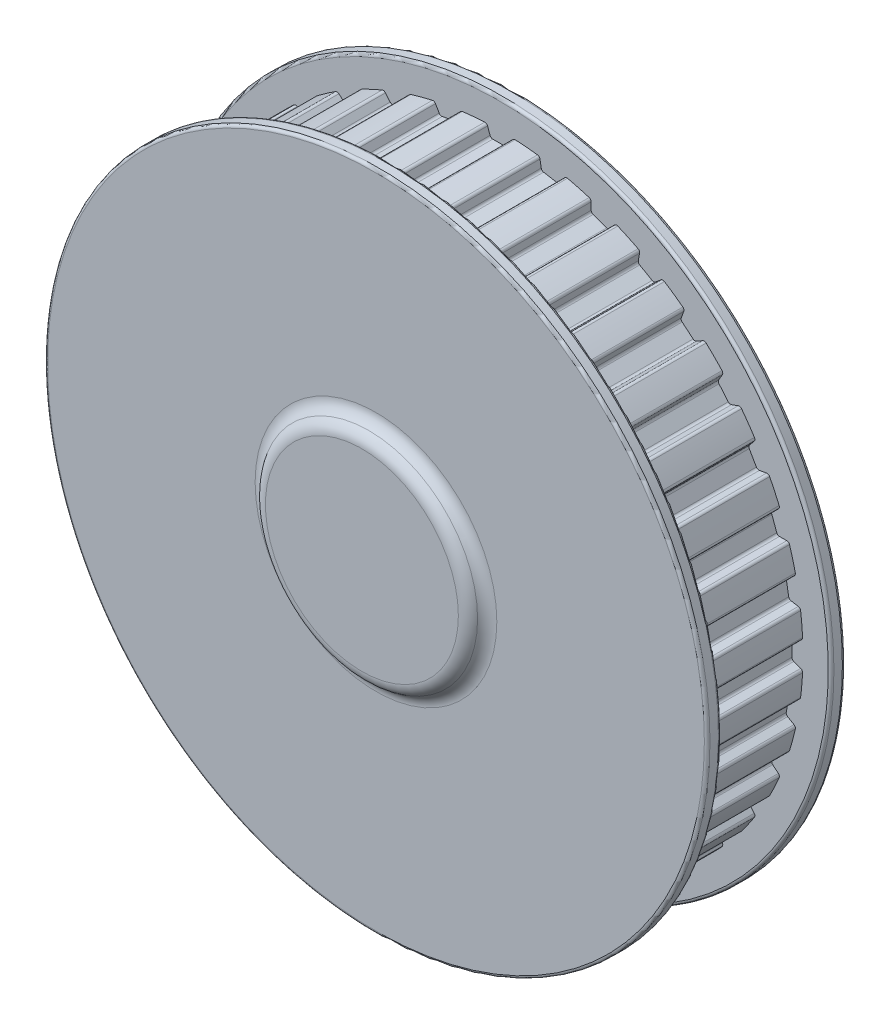
SolidWorks part; units mm, degrees
ref_plane "Front Plane" through (0, 0, 0) normal (0, 0, 1) x (1, 0, 0)
ref_plane "Top Plane" through (0, 0, 0) normal (0, 1, 0) x (1, 0, 0)
ref_plane "Right Plane" through (0, 0, 0) normal (1, 0, 0) x (0, 0, -1)
sketch "Sketch1" plane through (0, 0, 0) normal (0, 1, 0) x (1, 0, 0)
  line L0 (0, 36.1296) -> (0, -19.4741) construction
sketch "Sketch7" plane through (0, 0, 0) normal (0, 0, 1) x (1, 0, 0)
  line L0 (0, 0) -> (0, 52.7795) construction
  line L1 (-2.325, 53.7345) -> (-2.9401, 55.4245) construction
  line L2 (-2.325, 53.7345) -> (-1.6298, 51.8245) construction
  line L3 (-1.6298, 51.8245) -> (1.6298, 51.8245) construction
  line L4 (1.6298, 51.8245) -> (2.325, 53.7345) construction
  line L5 (2.325, 53.7345) -> (-2.325, 53.7345) construction
  line L6 (0, 51.8245) -> (0, 53.7345) construction
  line L7 (2.325, 53.7345) -> (2.9401, 55.4245) construction
  line L8 (-2.9401, 55.4245) -> (2.9401, 55.4245) construction
  line L9 (0, 0) -> (9.1651, 51.9776) construction
  line L10 (9.1651, 51.9776) -> (9.3396, 52.9676) construction
  line L11 (0, 53.7345) -> (0, 53.7847) construction
  line L12 (0, 53.7847) -> (0, 55.5024) construction
  line L13 (0, 54.6436) -> (9.4888, 53.8134) construction
  line L14 (9.3396, 52.9676) -> (9.6379, 54.6592) construction
  circle A1 centre (0, 0) radius 52.7795 construction
  circle A2 centre (-1.2727, 52.3345) radius 0.51 construction
  circle A3 centre (1.2727, 52.3345) radius 0.51 construction
  circle A4 centre (0, 0) radius 53.7847
  circle A5 centre (0, 0) radius 55.5024 construction
  dimension "D3" = 40
  dimension "D6" = 1.02
  dimension "D1" = 3.6
  dimension "D2" = 10
  dimension "D7" = 9.525
  dimension "D4" = 1.91
  dimension "D5" = 4.65
extrude "Boss-Extrude1" add sketch "Sketch7" along normal blind 7.25 and the other way blind 7.25 contours A4 region at (0, 0, 0)
sketch "Sketch14" plane through (0, 0, 0) normal (1, 0, 0) x (0, 0, -1)
  line L0 (-18, 0) -> (-18, 10)
  line L1 (-18, 0) -> (0, 0)
  line L2 (0, 0) -> (0, 19)
  line L3 (0, 19) -> (-7.25, 19)
  line L4 (-7.25, 19) -> (-18, 10)
  line L5 (-7.25, 53.7847) -> (-7.25, -53.7847) construction
  line L6 (-18, 6.7395) -> (-3.3555, 19) construction
  arc A0 (-7.25, 19) -> (-18, 10) centre (-18.1316, 21.0773) cw
  dimension "D1" = 10
  dimension "D2" = 19
  dimension "D3" = 18
  dimension "D4" = 2.5
revolve "Revolve1" add sketch "Sketch14" angle 360 about L0 region at (0, 7.5733, 7.5341) region at (0, 9.2725, 16.1663) region at (0, 17.2765, 6.6188)
sketch "Sketch9" plane through (0, 0, 0) normal (0, 0, 1) x (1, 0, 0)
  line L0 (2, 0) -> (-2, 0) construction
  line L1 (-2, 0) -> (-2, 7.5) construction
  line L2 (-2, 7.5) -> (2, 7.5) construction
  line L3 (2, 7.5) -> (2, 0) construction
  circle A0 centre (0, 0) radius 6 construction
  dimension "D1" = 12
  dimension "D2" = 4
  dimension "D3" = 7.5
sketch "Sketch10" plane through (0, 0, 0) normal (0, 0, 1) x (1, 0, 0)
  line L0 (2, 0) -> (-2, 0) construction
  line L1 (-2.2, 7.7) -> (2.2, 7.7)
  line L2 (-2.2, 7.7) -> (-2.2, 0)
  line L3 (-2.2, 0) -> (2.2, 0)
  line L4 (2.2, 7.7) -> (2.2, 0)
  line L5 (-2, 7.5) -> (2, 7.5) construction
  line L6 (2, 7.5) -> (2, 0) construction
  circle A0 centre (0, 0) radius 6.2
  circle A1 centre (0, 0) radius 6 construction
  dimension "D1" = 0.2
  dimension "D2" = 0.2
  dimension "D3" = 0.2
extrude "Cut-Extrude3" cut sketch "Sketch10" against normal through all both and the other way through all contours A0 L4 L1 L2 | L2 A0 L4 L3 | L4 A0 L2 L3 region at (0, 6.8793, 0) region at (0, 3.0348, 0) region at (0, -0.8613, 0)
sketch "Sketch11" plane through (0, 0, 0) normal (0, 1, 0) x (1, 0, 0)
  line L0 (53.7847, 7.25) -> (-53.7847, 7.25) construction
  line L1 (11, 7.25) -> (17.5, 7.25)
  line L2 (11, 7.25) -> (11, 4.75)
  line L3 (11, 4.75) -> (17.5, 4.75)
  line L4 (17.5, 7.25) -> (17.5, 4.75)
  line L5 (-53.7847, -7.25) -> (53.7847, -7.25) construction
  line L6 (11, -7.25) -> (17.5, -7.25)
  line L7 (11, -7.25) -> (11, -4.75)
  line L8 (11, -4.75) -> (17.5, -4.75)
  line L9 (17.5, -7.25) -> (17.5, -4.75)
  line L11 (11, 4.75) -> (11, -4.75) construction
  line L12 (17.5, -4.75) -> (17.5, 4.75) construction
  line L13 (6.2, 7.25) -> (-6.2, 7.25) construction
  line L14 (0, 7.25) -> (22.5, 7.25)
  line L15 (0, 7.25) -> (0, -7.25)
  line L16 (0, -7.25) -> (22.5, -7.25)
  line L17 (22.5, 7.25) -> (22.5, -7.25)
  line L18 (-6.2, -7.25) -> (6.2, -7.25) construction
  line L19 (6, 7.25) -> (6, -7.25) construction
  dimension "D1" = 22.5
  dimension "D2" = 6
  dimension "D3" = 5
  dimension "D4" = 5
  dimension "D5" = 2.5
sketch "Sketch15" plane through (0, 0, -7.25) normal (0, 0, -1) x (-1, 0, 0)
  circle A0 centre (0, 0) radius 8.0081
  circle A1 centre (0, 0) radius 2.25
  dimension "D1" = 4.5
extrude "Boss-Extrude2" add sketch "Sketch15" against normal blind 5.5
sketch "Sketch16" plane through (0, 0, -7.25) normal (0, 0, -1) x (-1, 0, 0)
  circle A0 centre (0, 0) radius 5
  dimension "D1" = 10
extrude "Cut-Extrude4" cut sketch "Sketch16" against normal blind 3
sketch "Sketch17" plane through (0, 0, -7.25) normal (0, 0, -1) x (-1, 0, 0)
  circle A0 centre (0, 0) radius 53.7847
  circle A1 centre (0, 0) radius 53.7847 construction
  circle A2 centre (0, 0) radius 5
  circle A3 centre (0, 0) radius 5 construction
extrude "Boss-Extrude3" add sketch "Sketch17" along normal blind 7.5
sketch "Sketch8" plane through (0, 0, 0) normal (0, 0, 1) x (1, 0, 0)
  line L6 (-1.6298, 51.8245) -> (-2.3433, 53.7847)
  line L7 (-2.3433, 53.7847) -> (2.3433, 53.7847)
  line L8 (2.3433, 53.7847) -> (1.6298, 51.8245)
  line L9 (1.6298, 51.8245) -> (-1.6298, 51.8245)
  line L10 (-2.325, 53.7345) -> (-1.6298, 51.8245) construction
  line L11 (1.6298, 51.8245) -> (2.325, 53.7345) construction
  line L12 (7.3942, 51.3201) -> (7.0319, 53.3745)
  line L13 (7.0319, 53.3745) -> (11.6473, 52.5607)
  line L14 (11.6473, 52.5607) -> (10.6043, 50.7541)
  line L15 (10.6043, 50.7541) -> (7.3942, 51.3201)
  line L16 (16.1935, 49.2565) -> (16.1935, 51.3426)
  line L17 (16.1935, 51.3426) -> (20.5974, 49.7397)
  line L18 (20.5974, 49.7397) -> (19.2565, 48.1416)
  line L19 (19.2565, 48.1416) -> (16.1935, 49.2565)
  line L20 (24.5008, 45.6962) -> (24.863, 47.7506)
  line L21 (24.863, 47.7506) -> (28.9217, 45.4073)
  line L22 (28.9217, 45.4073) -> (27.3237, 44.0664)
  line L23 (27.3237, 44.0664) -> (24.5008, 45.6962)
  line L24 (32.0636, 40.7475) -> (32.7771, 42.7077)
  line L25 (32.7771, 42.7077) -> (36.3672, 39.6953)
  line L26 (36.3672, 39.6953) -> (34.5606, 38.6522)
  line L27 (34.5606, 38.6522) -> (32.0636, 40.7475)
  line L28 (38.6522, 34.5606) -> (39.6953, 36.3672)
  line L29 (39.6953, 36.3672) -> (42.7077, 32.7771)
  line L30 (42.7077, 32.7771) -> (40.7475, 32.0636)
  line L31 (40.7475, 32.0636) -> (38.6522, 34.5606)
  line L32 (44.0664, 27.3237) -> (45.4073, 28.9217)
  line L33 (45.4073, 28.9217) -> (47.7506, 24.863)
  line L34 (47.7506, 24.863) -> (45.6962, 24.5008)
  line L35 (45.6962, 24.5008) -> (44.0664, 27.3237)
  line L36 (48.1416, 19.2565) -> (49.7397, 20.5974)
  line L37 (49.7397, 20.5974) -> (51.3426, 16.1935)
  line L38 (51.3426, 16.1935) -> (49.2565, 16.1935)
  line L39 (49.2565, 16.1935) -> (48.1416, 19.2565)
  line L40 (50.7541, 10.6043) -> (52.5607, 11.6473)
  line L41 (52.5607, 11.6473) -> (53.3745, 7.0319)
  line L42 (53.3745, 7.0319) -> (51.3201, 7.3942)
  line L43 (51.3201, 7.3942) -> (50.7541, 10.6043)
  line L44 (51.8245, 1.6298) -> (53.7847, 2.3433)
  line L45 (53.7847, 2.3433) -> (53.7847, -2.3433)
  line L46 (53.7847, -2.3433) -> (51.8245, -1.6298)
  line L47 (51.8245, -1.6298) -> (51.8245, 1.6298)
  line L48 (51.3201, -7.3942) -> (53.3745, -7.0319)
  line L49 (53.3745, -7.0319) -> (52.5607, -11.6473)
  line L50 (52.5607, -11.6473) -> (50.7541, -10.6043)
  line L51 (50.7541, -10.6043) -> (51.3201, -7.3942)
  line L52 (49.2565, -16.1935) -> (51.3426, -16.1935)
  line L53 (51.3426, -16.1935) -> (49.7397, -20.5974)
  line L54 (49.7397, -20.5974) -> (48.1416, -19.2565)
  line L55 (48.1416, -19.2565) -> (49.2565, -16.1935)
  line L56 (45.6962, -24.5008) -> (47.7506, -24.863)
  line L57 (47.7506, -24.863) -> (45.4073, -28.9217)
  line L58 (45.4073, -28.9217) -> (44.0664, -27.3237)
  line L59 (44.0664, -27.3237) -> (45.6962, -24.5008)
  line L60 (40.7475, -32.0636) -> (42.7077, -32.7771)
  line L61 (42.7077, -32.7771) -> (39.6953, -36.3672)
  line L62 (39.6953, -36.3672) -> (38.6522, -34.5606)
  line L63 (38.6522, -34.5606) -> (40.7475, -32.0636)
  line L64 (34.5606, -38.6522) -> (36.3672, -39.6953)
  line L65 (36.3672, -39.6953) -> (32.7771, -42.7077)
  line L66 (32.7771, -42.7077) -> (32.0636, -40.7475)
  line L67 (32.0636, -40.7475) -> (34.5606, -38.6522)
  line L68 (27.3237, -44.0664) -> (28.9217, -45.4073)
  line L69 (28.9217, -45.4073) -> (24.863, -47.7506)
  line L70 (24.863, -47.7506) -> (24.5008, -45.6962)
  line L71 (24.5008, -45.6962) -> (27.3237, -44.0664)
  line L72 (19.2565, -48.1416) -> (20.5974, -49.7397)
  line L73 (20.5974, -49.7397) -> (16.1935, -51.3426)
  line L74 (16.1935, -51.3426) -> (16.1935, -49.2565)
  line L75 (16.1935, -49.2565) -> (19.2565, -48.1416)
  line L76 (10.6043, -50.7541) -> (11.6473, -52.5607)
  line L77 (11.6473, -52.5607) -> (7.0319, -53.3745)
  line L78 (7.0319, -53.3745) -> (7.3942, -51.3201)
  line L79 (7.3942, -51.3201) -> (10.6043, -50.7541)
  line L80 (1.6298, -51.8245) -> (2.3433, -53.7847)
  line L81 (2.3433, -53.7847) -> (-2.3433, -53.7847)
  line L82 (-2.3433, -53.7847) -> (-1.6298, -51.8245)
  line L83 (-1.6298, -51.8245) -> (1.6298, -51.8245)
  line L84 (-7.3942, -51.3201) -> (-7.0319, -53.3745)
  line L85 (-7.0319, -53.3745) -> (-11.6473, -52.5607)
  line L86 (-11.6473, -52.5607) -> (-10.6043, -50.7541)
  line L87 (-10.6043, -50.7541) -> (-7.3942, -51.3201)
  line L88 (-16.1935, -49.2565) -> (-16.1935, -51.3426)
  line L89 (-16.1935, -51.3426) -> (-20.5974, -49.7397)
  line L90 (-20.5974, -49.7397) -> (-19.2565, -48.1416)
  line L91 (-19.2565, -48.1416) -> (-16.1935, -49.2565)
  line L92 (-24.5008, -45.6962) -> (-24.863, -47.7506)
  line L93 (-24.863, -47.7506) -> (-28.9217, -45.4073)
  line L94 (-28.9217, -45.4073) -> (-27.3237, -44.0664)
  line L95 (-27.3237, -44.0664) -> (-24.5008, -45.6962)
  line L96 (-32.0636, -40.7475) -> (-32.7771, -42.7077)
  line L97 (-32.7771, -42.7077) -> (-36.3672, -39.6953)
  line L98 (-36.3672, -39.6953) -> (-34.5606, -38.6522)
  line L99 (-34.5606, -38.6522) -> (-32.0636, -40.7475)
  line L100 (-38.6522, -34.5606) -> (-39.6953, -36.3672)
  line L101 (-39.6953, -36.3672) -> (-42.7077, -32.7771)
  line L102 (-42.7077, -32.7771) -> (-40.7475, -32.0636)
  line L103 (-40.7475, -32.0636) -> (-38.6522, -34.5606)
  line L104 (-44.0664, -27.3237) -> (-45.4073, -28.9217)
  line L105 (-45.4073, -28.9217) -> (-47.7506, -24.863)
  line L106 (-47.7506, -24.863) -> (-45.6962, -24.5008)
  line L107 (-45.6962, -24.5008) -> (-44.0664, -27.3237)
  line L108 (-48.1416, -19.2565) -> (-49.7397, -20.5974)
  line L109 (-49.7397, -20.5974) -> (-51.3426, -16.1935)
  line L110 (-51.3426, -16.1935) -> (-49.2565, -16.1935)
  line L111 (-49.2565, -16.1935) -> (-48.1416, -19.2565)
  line L112 (-50.7541, -10.6043) -> (-52.5607, -11.6473)
  line L113 (-52.5607, -11.6473) -> (-53.3745, -7.0319)
  line L114 (-53.3745, -7.0319) -> (-51.3201, -7.3942)
  line L115 (-51.3201, -7.3942) -> (-50.7541, -10.6043)
  line L116 (-51.8245, -1.6298) -> (-53.7847, -2.3433)
  line L117 (-53.7847, -2.3433) -> (-53.7847, 2.3433)
  line L118 (-53.7847, 2.3433) -> (-51.8245, 1.6298)
  line L119 (-51.8245, 1.6298) -> (-51.8245, -1.6298)
  line L120 (-51.3201, 7.3942) -> (-53.3745, 7.0319)
  line L121 (-53.3745, 7.0319) -> (-52.5607, 11.6473)
  line L122 (-52.5607, 11.6473) -> (-50.7541, 10.6043)
  line L123 (-50.7541, 10.6043) -> (-51.3201, 7.3942)
  line L124 (-49.2565, 16.1935) -> (-51.3426, 16.1935)
  line L125 (-51.3426, 16.1935) -> (-49.7397, 20.5974)
  line L126 (-49.7397, 20.5974) -> (-48.1416, 19.2565)
  line L127 (-48.1416, 19.2565) -> (-49.2565, 16.1935)
  line L128 (-45.6962, 24.5008) -> (-47.7506, 24.863)
  line L129 (-47.7506, 24.863) -> (-45.4073, 28.9217)
  line L130 (-45.4073, 28.9217) -> (-44.0664, 27.3237)
  line L131 (-44.0664, 27.3237) -> (-45.6962, 24.5008)
  line L132 (-40.7475, 32.0636) -> (-42.7077, 32.7771)
  line L133 (-42.7077, 32.7771) -> (-39.6953, 36.3672)
  line L134 (-39.6953, 36.3672) -> (-38.6522, 34.5606)
  line L135 (-38.6522, 34.5606) -> (-40.7475, 32.0636)
  line L136 (-34.5606, 38.6522) -> (-36.3672, 39.6953)
  line L137 (-36.3672, 39.6953) -> (-32.7771, 42.7077)
  line L138 (-32.7771, 42.7077) -> (-32.0636, 40.7475)
  line L139 (-32.0636, 40.7475) -> (-34.5606, 38.6522)
  line L140 (-27.3237, 44.0664) -> (-28.9217, 45.4073)
  line L141 (-28.9217, 45.4073) -> (-24.863, 47.7506)
  line L142 (-24.863, 47.7506) -> (-24.5008, 45.6962)
  line L143 (-24.5008, 45.6962) -> (-27.3237, 44.0664)
  line L144 (-19.2565, 48.1416) -> (-20.5974, 49.7397)
  line L145 (-20.5974, 49.7397) -> (-16.1935, 51.3426)
  line L146 (-16.1935, 51.3426) -> (-16.1935, 49.2565)
  line L147 (-16.1935, 49.2565) -> (-19.2565, 48.1416)
  line L148 (-10.6043, 50.7541) -> (-11.6473, 52.5607)
  line L149 (-11.6473, 52.5607) -> (-7.0319, 53.3745)
  line L150 (-7.0319, 53.3745) -> (-7.3942, 51.3201)
  line L151 (-7.3942, 51.3201) -> (-10.6043, 50.7541)
  circle A0 centre (0, 0) radius 53.7847 construction
  point P119 (0, 0)
  dimension "D1" = 36
extrude "Cut-Extrude2" cut sketch "Sketch8" against normal through all both and the other way through all
fillet "Fillet2" radius 0.51 144 edges at (32.7588, -42.6575, -3.75) (36.3209, -39.6685, -3.75) (39.6685, -36.3209, -3.75) (42.6575, -32.7588, -3.75) (45.3729, -28.8807, -3.75) (47.6979, -24.8537, -3.75) (49.6987, -20.5631, -3.75) (51.2891, -16.1935, -3.75) (52.5144, -11.6206, -3.75) (53.3218, -7.0412, -3.75) (53.7345, -2.325, -3.75) (53.7345, 2.325, -3.75) (53.3218, 7.0412, -3.75) (52.5144, 11.6206, -3.75) (51.2891, 16.1935, -3.75) (49.6987, 20.5631, -3.75) (47.6979, 24.8537, -3.75) (45.3729, 28.8807, -3.75) (42.6575, 32.7588, -3.75) (39.6685, 36.3209, -3.75) (36.3209, 39.6685, -3.75) (32.7588, 42.6575, -3.75) (28.8807, 45.3729, -3.75) (24.8537, 47.6979, -3.75) (20.5631, 49.6987, -3.75) (16.1935, 51.2891, -3.75) (11.6206, 52.5144, -3.75) (7.0412, 53.3218, -3.75) (2.325, 53.7345, -3.75) (32.0636, -40.7475, -3.75) (34.5606, -38.6522, -3.75) (38.6522, -34.5606, -3.75) (40.7475, -32.0636, -3.75) (44.0664, -27.3237, -3.75) (45.6962, -24.5008, -3.75) (48.1416, -19.2565, -3.75) (49.2565, -16.1935, -3.75) (50.7541, -10.6043, -3.75) (51.3201, -7.3942, -3.75) (51.8245, -1.6298, -3.75) (51.8245, 1.6298, -3.75) (51.3201, 7.3942, -3.75) (50.7541, 10.6043, -3.75) (49.2565, 16.1935, -3.75) (48.1416, 19.2565, -3.75) (45.6962, 24.5008, -3.75) (44.0664, 27.3237, -3.75) (40.7475, 32.0636, -3.75) (38.6522, 34.5606, -3.75) (34.5606, 38.6522, -3.75) (32.0636, 40.7475, -3.75) (27.3237, 44.0664, -3.75) (24.5008, 45.6962, -3.75) (19.2565, 48.1416, -3.75) (16.1935, 49.2565, -3.75) (10.6043, 50.7541, -3.75) (7.3942, 51.3201, -3.75) (1.6298, 51.8245, -3.75) (-1.6298, 51.8245, -3.75) (-2.325, 53.7345, -3.75) (-11.6206, -52.5144, -3.75) (-10.6043, -50.7541, -3.75) (-7.3942, -51.3201, -3.75) (-7.0412, -53.3218, -3.75) (-2.325, -53.7345, -3.75) (-1.6298, -51.8245, -3.75) (1.6298, -51.8245, -3.75) (2.325, -53.7345, -3.75) (7.0412, -53.3218, -3.75) (7.3942, -51.3201, -3.75) (10.6043, -50.7541, -3.75) (11.6206, -52.5144, -3.75) (16.1935, -51.2891, -3.75) (16.1935, -49.2565, -3.75) (19.2565, -48.1416, -3.75) (20.5631, -49.6987, -3.75) (24.8537, -47.6979, -3.75) (24.5008, -45.6962, -3.75) (27.3237, -44.0664, -3.75) (28.8807, -45.3729, -3.75) (-16.1935, -51.2891, -3.75) (-16.1935, -49.2565, -3.75) (-19.2565, -48.1416, -3.75) (-20.5631, -49.6987, -3.75) (-24.8537, -47.6979, -3.75) (-24.5008, -45.6962, -3.75) (-27.3237, -44.0664, -3.75) (-28.8807, -45.3729, -3.75) (-32.7588, -42.6575, -3.75) (-32.0636, -40.7475, -3.75) (-34.5606, -38.6522, -3.75) (-36.3209, -39.6685, -3.75) (-39.6685, -36.3209, -3.75) (-38.6522, -34.5606, -3.75) (-40.7475, -32.0636, -3.75) (-42.6575, -32.7588, -3.75) (-34.5606, 38.6522, -3.75) (-32.0636, 40.7475, -3.75) (-32.7588, 42.6575, -3.75) (-28.8807, 45.3729, -3.75) (-27.3237, 44.0664, -3.75) (-24.5008, 45.6962, -3.75) (-24.8537, 47.6979, -3.75) (-20.5631, 49.6987, -3.75) (-19.2565, 48.1416, -3.75) (-16.1935, 49.2565, -3.75) (-16.1935, 51.2891, -3.75) (-11.6206, 52.5144, -3.75) (-10.6043, 50.7541, -3.75) (-7.3942, 51.3201, -3.75) (-45.3729, -28.8807, -3.75) (-44.0664, -27.3237, -3.75) (-45.6962, -24.5008, -3.75) (-47.6979, -24.8537, -3.75) (-49.6987, -20.5631, -3.75) (-48.1416, -19.2565, -3.75) (-49.2565, -16.1935, -3.75) (-51.2891, -16.1935, -3.75) (-52.5144, -11.6206, -3.75) (-50.7541, -10.6043, -3.75) (-51.3201, -7.3942, -3.75) (-53.3218, -7.0412, -3.75) (-53.7345, -2.325, -3.75) (-51.8245, -1.6298, -3.75) (-51.8245, 1.6298, -3.75) (-53.7345, 2.325, -3.75) (-53.3218, 7.0412, -3.75) (-51.3201, 7.3942, -3.75) (-50.7541, 10.6043, -3.75) (-52.5144, 11.6206, -3.75) (-51.2891, 16.1935, -3.75) (-49.2565, 16.1935, -3.75) (-48.1416, 19.2565, -3.75) (-49.6987, 20.5631, -3.75) (-47.6979, 24.8537, -3.75) (-45.6962, 24.5008, -3.75) (-44.0664, 27.3237, -3.75) (-45.3729, 28.8807, -3.75) (-42.6575, 32.7588, -3.75) (-40.7475, 32.0636, -3.75) (-38.6522, 34.5606, -3.75) (-39.6685, 36.3209, -3.75) (-36.3209, 39.6685, -3.75) (-7.0412, 53.3218, -3.75)
sketch "Sketch18" plane through (0, 0, -14.75) normal (0, 0, -1) x (-1, 0, 0)
  circle A0 centre (0, 0) radius 5
  circle A1 centre (0, 0) radius 58.7847
  circle A2 centre (0, 0) radius 53.7847
  circle A3 centre (0, 0) radius 5 construction
  circle A4 centre (0, 0) radius 53.7847 construction
  dimension "D1" = 5
extrude "Boss-Extrude4" add sketch "Sketch18" along normal blind 2.5 contours A1 A2 | A2 A0 region at (57.1221, 0, -14.75) region at (52.2635, 0, -14.75)
sketch "Sketch19" plane through (0, 0, 7.25) normal (0, 0, 1) x (1, 0, 0)
  circle A0 centre (0, 0) radius 19
  circle A1 centre (0, 0) radius 58.7847
  circle A2 centre (0, 0) radius 58.7847 construction
  circle A3 centre (0, 0) radius 19 construction
extrude "Boss-Extrude5" add sketch "Sketch19" against normal blind 2.5
sketch "Sketch20" plane through (0, 0, 18) normal (0, 0, 1) x (1, 0, 0)
  line L0 (-2.2, 5.7966) -> (-2.2, 7.7)
  line L1 (-2.2, 7.7) -> (2.2, 7.7)
  line L2 (-2.2, 7.7) -> (2.2, 7.7) construction
  line L3 (2.2, 7.7) -> (2.2, 5.7966)
  circle A0 centre (0, 0) radius 6.2
  arc A1 (-2.2, 5.7966) -> (2.2, 5.7966) centre (0, 0) ccw construction
  arc M2 (2.2, 5.7966) -> (-2.2, 5.7966) centre (0, 0) cw
  line M3 (-2.2, 5.7966) -> (-2.2, 7.7)
  line M4 (-2.2, 7.7) -> (2.2, 7.7)
  line M5 (2.2, 7.7) -> (2.2, 5.7966)
extrude "Cut-Extrude5" cut sketch "Sketch20" against normal through all contours A0 M5 M4 M3 | A0 M2 region at (0, 6.8793, 18) region at (0, 0, 18)
fillet "Fillet3" radius 0.5 12 edges at (2.2, 5.7966, 0.375) (-2.2, 5.7966, 0.375) (2.2, 6.7483, 18) (-2.2, 6.7483, 18) (0, 7.7, 18) (-19, 0, 7.25) (-10, 0, 18) (0, -6.2, 18) (58.7847, 0, 4.75) (-58.7847, 0, -14.75) (-58.7847, 0, -17.25) (58.7847, 0, 7.25)
sketch "Sketch21" plane through (0, 0, 0) normal (0, 0, 1) x (1, 0, 0)
  circle A0 centre (0, 0) radius 12.5
  dimension "D1" = 25
extrude "Cut-Extrude6" cut sketch "Sketch21" against normal through all both and the other way through all
sketch "Sketch22" plane through (0, 0, 7.25) normal (0, 0, 1) x (1, 0, 0)
  circle A0 centre (0, 0) radius 18.9519
extrude "Cut-Extrude7" cut sketch "Sketch22" along normal through all
extrude "Boss-Extrude6" add sketch "Sketch22<2>" along normal blind 2.5
sketch "Sketch22<2>" plane through (0, 0, 7.25) normal (0, 0, 1) x (1, 0, 0) same geometry as "Sketch22"
fillet "Fillet4" radius 2.5 1 edges at (18.9519, 0, 7.2593)
fillet "Fillet5" radius 2.5 1 edges at (18.9519, 0, 9.75)
